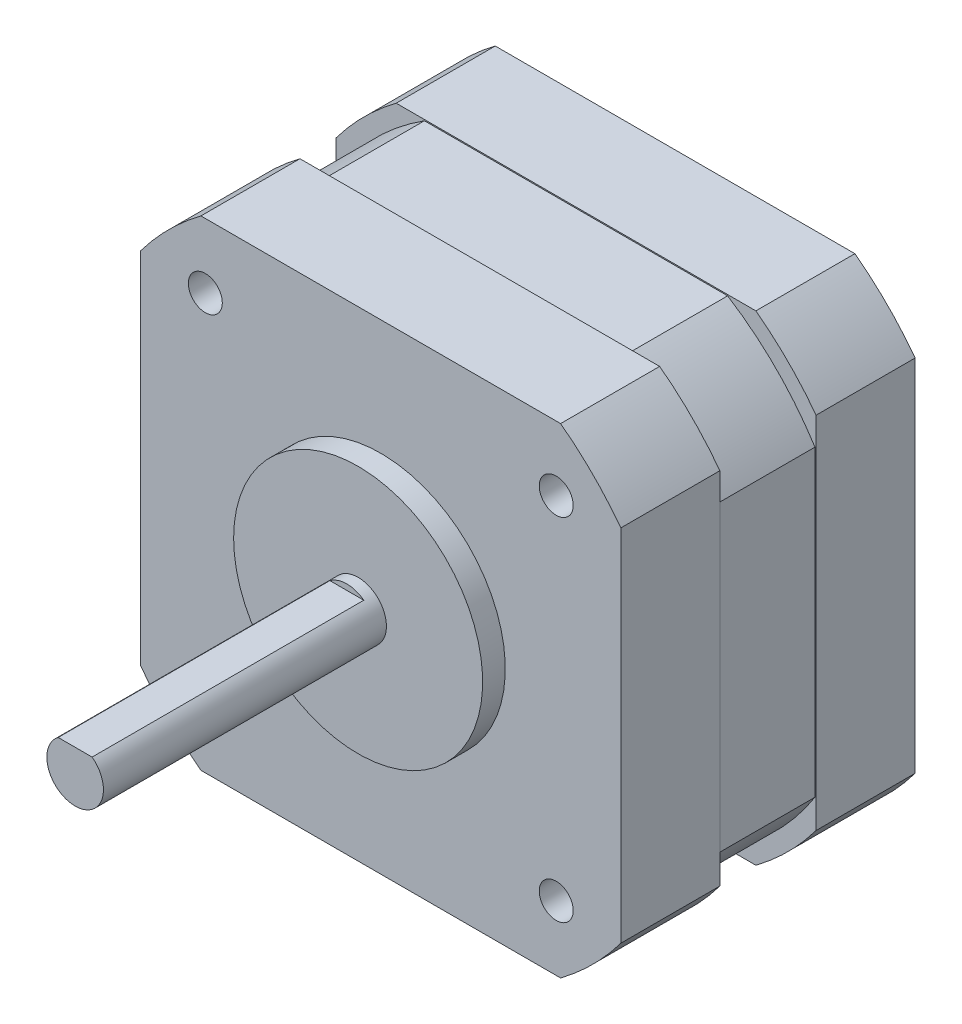
SolidWorks part; units mm, degrees
material "Plain Carbon Steel"
ref_plane "Front" through (0, 0, 0) normal (0, 0, 1) x (1, 0, 0)
ref_plane "Top" through (0, 0, 0) normal (0, 1, 0) x (1, 0, 0)
ref_plane "Right" through (0, 0, 0) normal (1, 0, 0) x (0, 0, -1)
sketch "Sketch1" plane through (0, 0, 0) normal (0, 0, 1) x (1, 0, 0)
  circle A0 centre (0, 0) radius 2.5
  dimension "D1" = 5
extrude "Boss-Extrude1" add sketch "Sketch1" along normal blind 27
sketch "Sketch2" plane through (0, 0, 0) normal (0, 0, -1) x (-1, 0, 0)
  circle A0 centre (0, 0) radius 11
  dimension "D1" = 22
extrude "Boss-Extrude2" add sketch "Sketch2" against normal blind 2
sketch "Sketch3" plane through (0, 0, 0) normal (0, 0, -1) x (-1, 0, 0)
  line L1 (21.209, -21.209) -> (-21.209, -21.209)
  line L2 (21.209, -21.209) -> (21.209, 21.209)
  line L3 (21.209, 21.209) -> (-21.209, 21.209)
  line L4 (-21.209, -21.209) -> (-21.209, 21.209)
  line L5 (21.209, -21.209) -> (-21.209, 21.209) construction
  line L6 (21.209, 21.209) -> (-21.209, -21.209) construction
  point P0 (0, 0)
  dimension "D1" = 42.418
extrude "Boss-Extrude3" add sketch "Sketch3" along normal blind 26
sketch "Sketch4" plane through (0, 0, -26) normal (0, 0, -1) x (-1, 0, 0)
  line L0 (-21.209, -15.888) -> (-21.209, -21.209)
  line L1 (15.888, -21.209) -> (21.209, -21.209)
  line L2 (21.209, 15.888) -> (21.209, 21.209)
  line L3 (-15.888, 21.209) -> (-21.209, 21.209)
  line L4 (-21.209, 21.209) -> (-21.209, -21.209)
  line L5 (-21.209, -21.209) -> (21.209, -21.209)
  line L6 (21.209, -21.209) -> (21.209, 21.209)
  line L7 (21.209, 21.209) -> (-21.209, 21.209)
  line L8 (-21.209, 21.209) -> (-21.209, 15.888)
  line L9 (-21.209, -21.209) -> (-15.888, -21.209)
  line L10 (21.209, -21.209) -> (21.209, -15.888)
  line L11 (21.209, 21.209) -> (15.888, 21.209)
  arc A0 (-21.209, -15.888) -> (-15.888, -21.209) centre (0, 0) ccw
  arc A1 (15.888, -21.209) -> (21.209, -15.888) centre (0, 0) ccw
  arc A2 (21.209, 15.888) -> (15.888, 21.209) centre (0, 0) ccw
  arc A3 (-15.888, 21.209) -> (-21.209, 15.888) centre (0, 0) ccw
  dimension "D2" = 26.5
  dimension "D1" = 0
extrude "Cut-Extrude1" cut sketch "Sketch4" against normal through all
hole_wizard "M3x0.5 Tapped Hole1" positions "Sketch6" profile "Sketch5" tap size "M3x0.5" standard "ANSI Metric"
sketch "Sketch6" plane through (0, 0, 0) normal (0, 0, 1) x (1, 0, 0)
  line L0 (-16.1632, 0) -> (0, 0) construction
  line L1 (0, 0) -> (0, 15.0764) construction
  point P0 (-15.5, 15.5)
  point P11 (-15.5, -15.5)
  point P12 (15.5, -15.5)
  point P13 (15.5, 15.5)
  dimension "D1" = 31
  dimension "D2" = 31
sketch "Sketch5" plane through (-15.5, 15.5, 0) normal (1, 0, 0) x (0, -1, 0)
  line L0 (0, 0) -> (0, 8.2511)
  line L1 (0, 8.2511) -> (1.25, 7.5)
  line L2 (1.25, 7.5) -> (1.25, 6)
  line L3 (1.25, 6) -> (1.5, 6)
  line L4 (1.5, 6) -> (1.5, 0)
  line L5 (1.5, 0) -> (0, 0)
  line L10 (0, 8.2511) -> (-1.25, 7.5) construction
  line L11 (0, -6.35) -> (0, 107.95) construction
  dimension "Tap Drill Dia." = 2.5
  dimension "Tap Drill Depth" = 7.5
  dimension "Thread Major Dia." = 3
  dimension "Thread Depth" = 6
  dimension "Drill Angle" = 118
sketch "Sketch7" plane through (0, 0, 27) normal (0, 0, 1) x (1, 0, 0)
  line L0 (-1.5, 2) -> (1.5, 2)
  circle A0 centre (0, 0) radius 2.5 construction
  circle A1 centre (0, 0) radius 2.5 construction
  arc A2 (1.5, 2) -> (-1.5, 2) centre (0, 0) ccw
  dimension "D1" = 4.5
extrude "Cut-Extrude2" cut sketch "Sketch7" against normal blind 24
ref_plane "Plane1" through (0, 0, -13) normal (0, 0, 1) x (1, 0, 0)
sketch "Sketch8" plane through (0, 0, -13) normal (0, 0, 1) x (1, 0, 0)
  line L0 (-13.3944, 21.109) -> (13.3944, 21.109)
  line L1 (-5.7152, 0) -> (0, 0) construction
  line L2 (0, 0) -> (0, 8.4579) construction
  line L3 (-15.888, 21.209) -> (15.888, 21.209) construction
  line L4 (-13.3944, -21.109) -> (13.3944, -21.109)
  line L5 (-21.109, 13.3944) -> (-21.109, -13.3944)
  line L6 (-21.209, -15.888) -> (-21.209, 15.888) construction
  line L7 (21.109, 13.3944) -> (21.109, -13.3944)
  line L12 (15.888, 21.209) -> (-15.888, 21.209)
  line L13 (-21.209, 15.888) -> (-21.209, -15.888)
  line L14 (-15.888, -21.209) -> (15.888, -21.209)
  line L15 (21.209, -15.888) -> (21.209, 15.888)
  line L16 (15.888, 21.209) -> (-15.888, 21.209)
  line L17 (-21.209, 15.888) -> (-21.209, -15.888)
  line L18 (-15.888, -21.209) -> (15.888, -21.209)
  line L19 (21.209, -15.888) -> (21.209, 15.888)
  arc A0 (-13.3944, 21.109) -> (-21.109, 13.3944) centre (0, 0) ccw
  arc A1 (-21.109, -13.3944) -> (-13.3944, -21.109) centre (0, 0) ccw
  arc A2 (21.109, 13.3944) -> (13.3944, 21.109) centre (0, 0) ccw
  arc A3 (13.3944, -21.109) -> (21.109, -13.3944) centre (0, 0) ccw
  arc A5 (-15.888, 21.209) -> (-21.209, 15.888) centre (0, 0) ccw
  arc A6 (-21.209, -15.888) -> (-15.888, -21.209) centre (0, 0) ccw
  arc A7 (15.888, -21.209) -> (21.209, -15.888) centre (0, 0) ccw
  arc A8 (21.209, 15.888) -> (15.888, 21.209) centre (0, 0) ccw
  arc A9 (-15.888, 21.209) -> (-21.209, 15.888) centre (0, 0) ccw
  arc A10 (-21.209, -15.888) -> (-15.888, -21.209) centre (0, 0) ccw
  arc A11 (15.888, -21.209) -> (21.209, -15.888) centre (0, 0) ccw
  arc A12 (21.209, 15.888) -> (15.888, 21.209) centre (0, 0) ccw
  dimension "D1" = 50
  dimension "D2" = 0.1
  dimension "D3" = 0.1
  dimension "D4" = 0
extrude "Cut-Extrude3" cut sketch "Sketch8" against normal offset from surface 8.75 and the other way offset from surface 8.75 up to face at (0, 0, -26) other way up to face at (-14, 15.5, 0)
